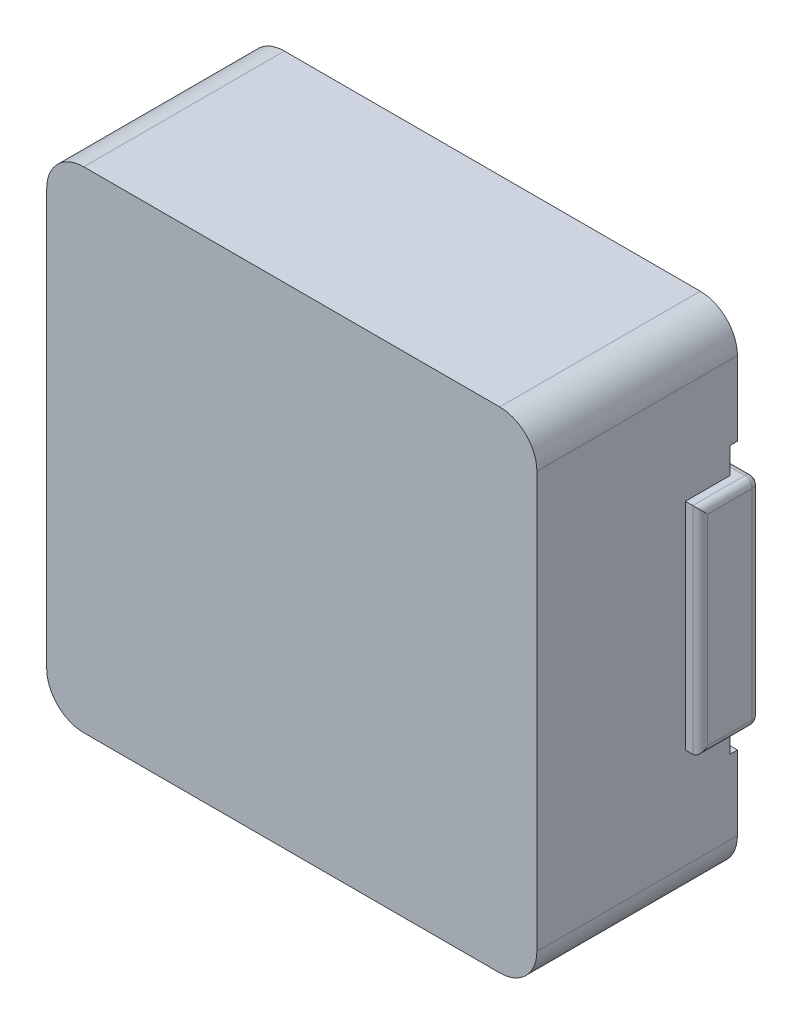
SolidWorks part; units mm, degrees
ref_plane "Front Plane" through (0, 0, 0) normal (0, 0, 1) x (1, 0, 0)
ref_plane "Top Plane" through (0, 0, 0) normal (0, 1, 0) x (1, 0, 0)
ref_plane "Right Plane" through (0, 0, 0) normal (1, 0, 0) x (0, 0, -1)
sketch "Sketch1" plane through (0, 0, 0) normal (0, 0, 1) x (1, 0, 0)
  line L1 (-3.3, -3.3) -> (3.3, -3.3)
  line L2 (-3.3, -3.3) -> (-3.3, 3.3)
  line L3 (-3.3, 3.3) -> (3.3, 3.3)
  line L4 (3.3, -3.3) -> (3.3, 3.3)
  line L5 (0, 3.3) -> (0, -3.3) construction
  line L6 (-3.3, 0) -> (3.3, 0) construction
  point P0 (0, 0)
  dimension "D1" = 6.6
  dimension "D2" = 6.6
extrude "Boss-Extrude1" add sketch "Sketch1" along normal blind 2.7 from offset 0.1
sketch "Sketch2" plane through (0, 0, 0) normal (0, 0, 1) x (1, 0, 0)
  line L0 (-3.3, 3.3) -> (-3.3, -3.3) construction
  line L1 (-5.3, -1.8) -> (-1.3, -1.8)
  line L2 (-5.3, -1.8) -> (-5.3, 1.8)
  line L3 (-5.3, 1.8) -> (-1.3, 1.8)
  line L4 (-1.3, -1.8) -> (-1.3, 1.8)
  line L5 (-3.3, 1.8) -> (-3.3, -1.8) construction
  line L6 (-5.3, 0) -> (-1.3, 0) construction
  line L7 (-3.3, 3.3) -> (-3.3, -3.3) construction
  point P0 (-3.3, 0)
  dimension "D1" = 2
  dimension "D2" = 3.6
extrude "Cut-Extrude1" cut sketch "Sketch2" along normal blind 0.1 from surface starting at face at (0, 0, 0.1)
mirror "Mirror1" about plane through (0, 0, 0) normal (1, 0, 0) of "Cut-Extrude1"
sketch "Sketch3" plane through (0, 0, 0) normal (0, 0, 1) x (1, 0, 0)
  line L1 (-1.9, -1.45) -> (-3.5, -1.45)
  line L2 (-1.9, -1.45) -> (-1.9, 1.45)
  line L3 (-1.9, 1.45) -> (-3.5, 1.45)
  line L4 (-3.5, -1.45) -> (-3.5, 1.45)
  line L5 (-2.7, 1.45) -> (-2.7, -1.45) construction
  line L6 (-1.9, 0) -> (-3.5, 0) construction
  point P0 (-2.7, 0)
  dimension "D1" = 3.5
  dimension "D2" = 1.6
  dimension "D3" = 2.9
extrude "Boss-Extrude2" add sketch "Sketch3" along normal blind 0.8
mirror "Mirror2" about plane through (0, 0, 0) normal (1, 0, 0) of "Boss-Extrude2"
fillet "Fillet1" radius 0.5 4 edges at (3.3, -3.3, 1.45) (-3.3, -3.3, 1.45) (-3.3, 3.3, 1.45) (3.3, 3.3, 1.45)
fillet "Fillet2" radius 0.1 15 edges at (3.5, -1.45, 0.4) (3.5, 0, 0.8) (3.5, 1.45, 0.4) (2.7, 1.45, 0) (1.9, 0, 0) (2.7, -1.45, 0) (3.5, 0, 0) (-2.7, -1.45, 0) (-1.9, 0, 0) (-2.7, 1.45, 0) (-3.5, 1.45, 0.4) (-3.5, 0, 0.8) (-3.5, -1.45, 0.4) (-3.5, 0, 0) (-2.6, 1.45, 0.2)
